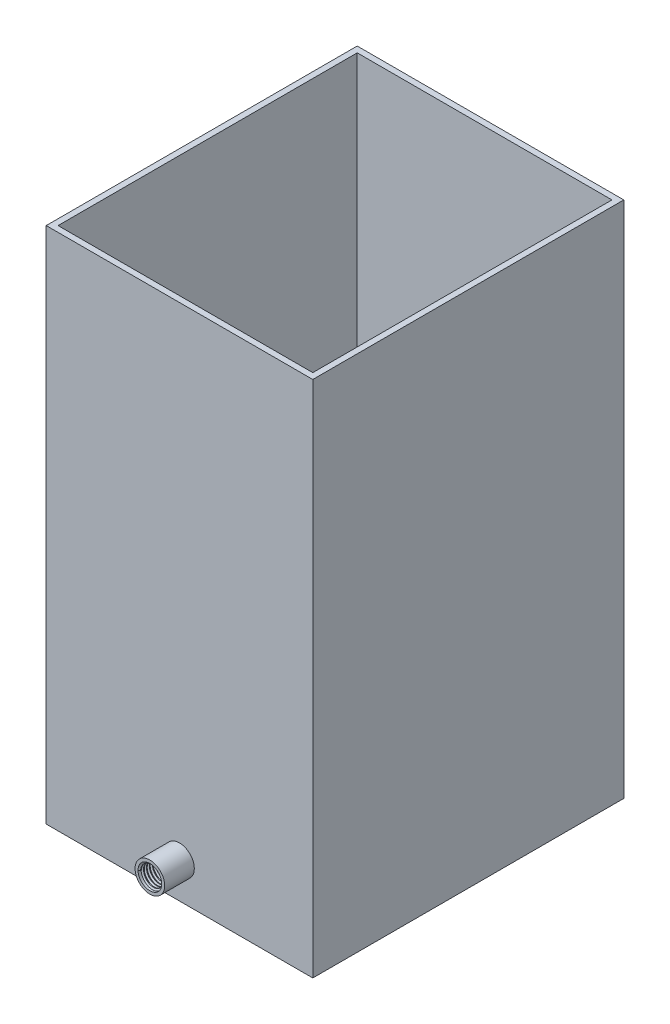
SolidWorks part; units mm, degrees
ref_plane "Front Plane" through (0, 0, 0) normal (0, 0, 1) x (1, 0, 0)
ref_plane "Top Plane" through (0, 0, 0) normal (0, 1, 0) x (1, 0, 0)
ref_plane "Right Plane" through (0, 0, 0) normal (1, 0, 0) x (0, 0, -1)
sketch "Sketch1" plane through (0, 0, 0) normal (0, 0, 1) x (1, 0, 0)
  line L0 (0, 0) -> (0, 106.5275) construction
  line L1 (-45, 0) -> (45, 0)
  line L2 (45, 0) -> (45, 175)
  line L3 (45, 175) -> (-45, 175)
  line L4 (-45, 175) -> (-45, 0)
  dimension "D1" = 90
  dimension "D2" = 175
extrude "Boss-Extrude1" add sketch "Sketch1" along normal blind 105
shell "Shell1" thickness 2 removed face at (0, 175, 52.5)
sketch "Sketch2" plane through (0, 0, 105) normal (0, 0, 1) x (1, 0, 0)
  line L0 (-45, 0) -> (45, 0) construction
  circle A0 centre (0, 12) radius 5
  circle A1 centre (0, 12) radius 4
  point P7 (0, 0)
  dimension "D1" = 10
  dimension "D2" = 8
  dimension "D3" = 12
extrude "Boss-Extrude2" add sketch "Sketch2" along normal blind 10
sketch "Sketch3" plane through (0, 0, 105) normal (0, 0, 1) x (1, 0, 0)
  circle A0 centre (0, 12) radius 4 construction
  circle A1 centre (0, 12) radius 4
extrude "Cut-Extrude1" cut sketch "Sketch3" against normal up to next
thread "Thread1" pitch 1 method extrude profile "Thread Profile1" start angle 0, offset 0, length 0, pitch 1, diameter 8
ref_plane "Plane1" through (-4, 12, 115) normal (0, -1, 0) x (-1, 0, 0)
sketch "Thread Profile1" plane through (-4, 12, 115) normal (0, -1, 0) x (-1, 0, 0)
  line L0 (0, 0) -> (0, 1) construction
  line L11 (0, 0) -> (0, 0.875)
  line L12 (0, 0.875) -> (-0.5413, 0.5625)
  line L13 (-0.5413, 0.5625) -> (-0.5413, 0.3125)
  line L15 (-0.5413, 0.3125) -> (0, 0)
  line L17 (-0.5413, 0.4375) -> (0, 0.4375) construction
  point P2 (0, 0)
  dimension "Pitch" = 1
  dimension "Profile_Angle" = 60
  dimension "Profile_Land" = 0.25
  dimension "Profile_Height" = 0.5413
sketch "Sketch4" plane through (0, 0, 0) normal (0, -1, 0) x (1, 0, 0)
  line L0 (-10, 65) -> (10, 65)
  line L1 (10, 65) -> (10, 57)
  line L2 (10, 57) -> (-10, 57)
  line L3 (-10, 57) -> (-10, 65)
  line L4 (0, 0) -> (0, 84.4966) construction
  line L5 (-45, 105) -> (45, 105) construction
  dimension "D1" = 20
  dimension "D2" = 40
  dimension "D3" = 8
extrude "Boss-Extrude3" add sketch "Sketch4" along normal blind 3
